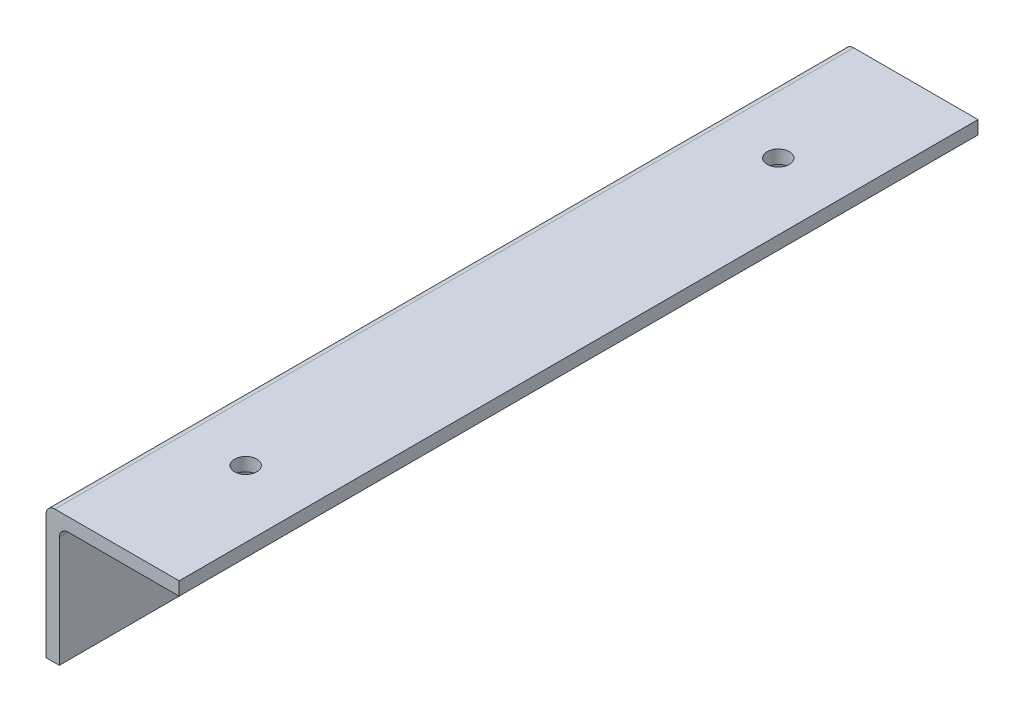
SolidWorks part; units mm, degrees
ref_plane "Plan de face" through (0, 0, 0) normal (0, 0, 1) x (1, 0, 0)
ref_plane "Plan de dessus" through (0, 0, 0) normal (0, 1, 0) x (1, 0, 0)
ref_plane "Plan de droite" through (0, 0, 0) normal (1, 0, 0) x (0, 0, -1)
sketch "Esquisse1" plane through (0, 0, 0) normal (0, 0, 1) x (1, 0, 0)
  line L0 (0, 0) -> (0, -30)
  line L1 (0, -30) -> (3, -30)
  line L2 (3, -30) -> (3, -3)
  line L3 (3, -3) -> (30, -3)
  line L4 (30, -3) -> (30, 0)
  line L5 (30, 0) -> (0, 0)
  dimension "D1" = 30
  dimension "D2" = 30
  dimension "D3" = 3
  dimension "D4" = 3
extrude "Boss.-Extru.1" add sketch "Esquisse1" along normal blind 180
sketch "Esquisse2" plane through (3, 0, 0) normal (1, 0, 0) x (0, 0, -1)
  line L0 (-180, -30) -> (0, -30) construction
  line L1 (-180, -30) -> (-180, -3) construction
  line L2 (0, -30) -> (0, -3) construction
  circle A0 centre (-25, -20) radius 3
  circle A1 centre (-155, -20) radius 3
  dimension "D1" = 6
  dimension "D2" = 6
  dimension "D3" = 10
  dimension "D4" = 10
  dimension "D5" = 25
  dimension "D6" = 25
extrude "Enlèv. mat.-Extru.1" cut sketch "Esquisse2" against normal blind 180
sketch "Esquisse3" plane through (0, -3, 0) normal (0, -1, 0) x (1, 0, 0)
  line L0 (3, 0) -> (30, 0) construction
  line L1 (3, 180) -> (30, 180) construction
  line L2 (30, 180) -> (0, 180) construction
  line L3 (0, 180) -> (0, 0) construction
  circle A0 centre (15, 150) radius 2.5
  circle A1 centre (15, 30) radius 2.5
  dimension "D1" = 5
  dimension "D2" = 5
  dimension "D3" = 30
  dimension "D4" = 30
  dimension "D5" = 120
  dimension "D6" = 180
  dimension "D7" = 15
  dimension "D8" = 15
extrude "Enlèv. mat.-Extru.2" cut sketch "Esquisse3" against normal blind 180
fillet "Congé1" radius 2 2 edges at (0, 0, 90) (3, -3, 90)
